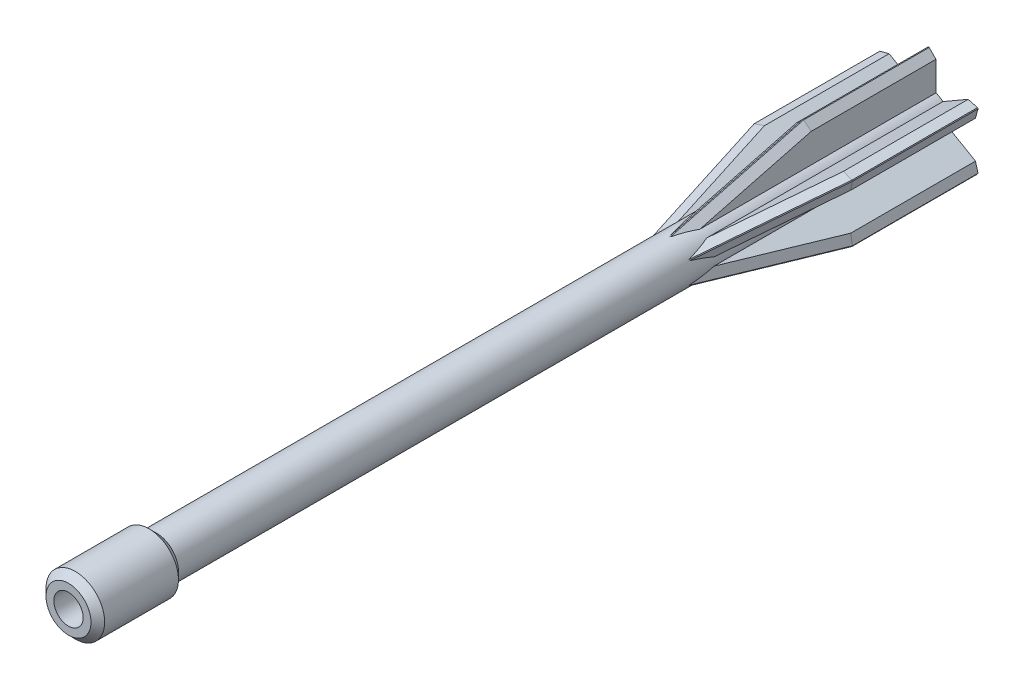
SolidWorks part; units mm, degrees
ref_plane "정면" through (0, 0, 0) normal (0, 0, 1) x (1, 0, 0)
ref_plane "윗면" through (0, 0, 0) normal (0, 1, 0) x (1, 0, 0)
ref_plane "우측면" through (0, 0, 0) normal (1, 0, 0) x (0, 0, -1)
sketch "스케치1" plane through (0, 0, 0) normal (0, 0, 1) x (1, 0, 0)
  circle A0 centre (0, 0) radius 2.25
  dimension "D1" = 4.5
extrude "보스-돌출1" add sketch "스케치1" along normal blind 80
sketch "스케치5" plane through (0, 0, 0) normal (1, 0, 0) x (0, 0, -1)
  line L0 (0, 1.3231) -> (0, 5.8)
  line L1 (0, 5.8) -> (-12.8495, 5.8)
  line L2 (-12.8495, 5.8) -> (-30, 1.3231)
  line L3 (-30, 1.3231) -> (0, 1.3231)
  line L4 (0, 1.3231) -> (0, 0) construction
  line L5 (0, 0) -> (-30, 0) construction
  line L6 (-30, 0) -> (-30, 1.3231) construction
  dimension "D1" = 30
  dimension "D2" = 5.8
extrude "보스-돌출3" add sketch "스케치5" along normal mid plane 1.5
chamfer "모따기4" distance 0.7 angle 45 4 edges at (-0.75, 3.9607, 19.8958) (-0.75, 5.8, 6.4248) (0.75, 5.8, 6.4248) (0.75, 3.9607, 19.8958)
pattern_circular "원형 패턴1" count 6 over 360 about axis through (0, 0, 80) along (0, 0, -1) of "보스-돌출3", "모따기4"
sketch "스케치7" plane through (0, 0, 80) normal (0, 0, 1) x (1, 0, 0)
  circle A0 centre (0, 0) radius 3
  dimension "D1" = 6
extrude "보스-돌출4" add sketch "스케치7" along normal blind 8
chamfer "모따기6" distance 1 angle 45 1 edges at (2.25, 0, 80)
chamfer "모따기7" distance 0.7 angle 45 1 edges at (3, 0, 88)
sketch "스케치8" plane through (0, 0, 88) normal (0, 0, 1) x (1, 0, 0)
  circle A0 centre (0, 0) radius 1.5
  dimension "D1" = 3
extrude "컷-돌출3" cut sketch "스케치8" against normal blind 75 contours A0
sketch "스케치9" plane through (0, 0, 0) normal (0, 0, 1) x (1, 0, 0)
  circle A0 centre (0, 0) radius 2
  dimension "D1" = 4
extrude "컷-돌출4" cut sketch "스케치9" along normal blind 1
chamfer "모따기8" distance 1 angle 45 1 edges at (2, 0, 1)
